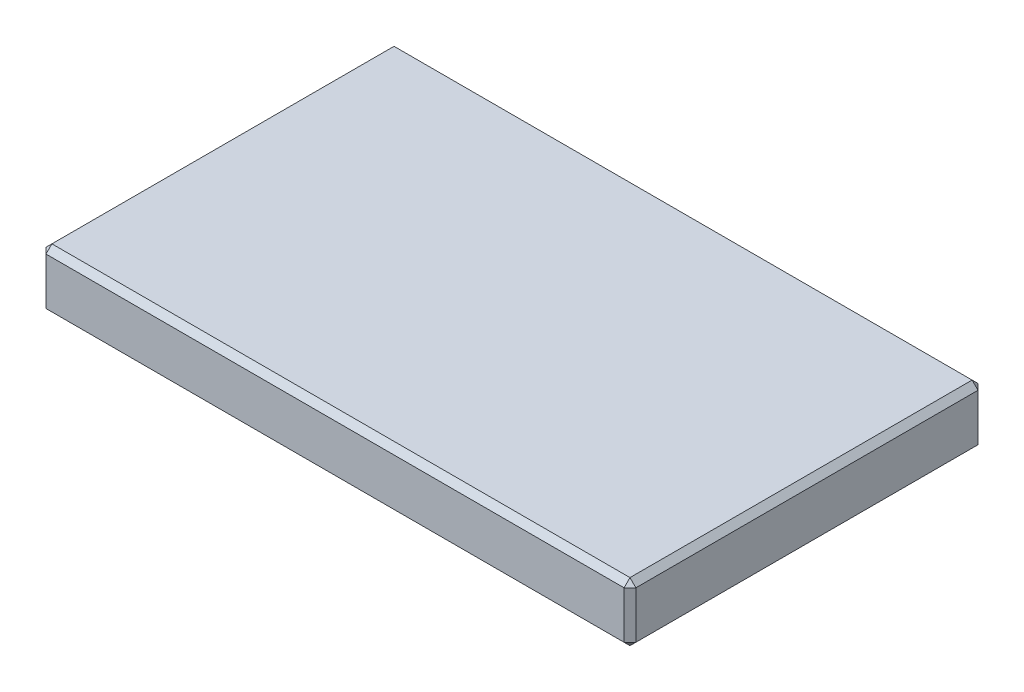
SolidWorks part; units mm, degrees
ref_plane "Front Plane" through (0, 0, 0) normal (0, 0, 1) x (1, 0, 0)
ref_plane "Top Plane" through (0, 0, 0) normal (0, 1, 0) x (1, 0, 0)
ref_plane "Right Plane" through (0, 0, 0) normal (1, 0, 0) x (0, 0, -1)
sketch "Sketch1" plane through (0, 0, 0) normal (0, 1, 0) x (1, 0, 0)
  line L0 (-250, 0) -> (250, 0) construction
  line L1 (250, -150) -> (-250, -150)
  line L2 (250, -150) -> (250, 150)
  line L3 (250, 150) -> (-250, 150)
  line L4 (-250, -150) -> (-250, 150)
  line L5 (250, -150) -> (-250, 150) construction
  line L6 (250, 150) -> (-250, -150) construction
  point P0 (0, 0)
  dimension "D1" = 500
  dimension "D2" = 300
extrude "Boss-Extrude1" add sketch "Sketch1" along normal blind 50
chamfer "Chamfer1" distance 5 angle 45 12 edges at (0, 0, 150) (250, 0, 0) (0, 0, -150) (-250, 0, 0) (0, 50, -150) (250, 25, -150) (250, 50, 0) (250, 25, 150) (0, 50, 150) (-250, 25, -150) (-250, 50, 0) (-250, 25, 150)
ref_axis "Axis1" through (275, 50, 0) along (-1, 0, 0)
